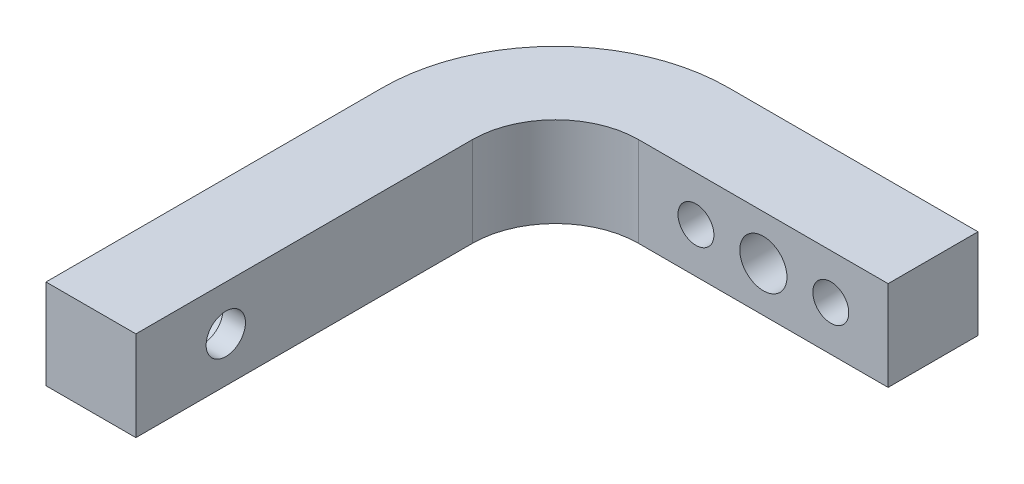
SolidWorks part; units mm, degrees
ref_plane "Front Plane" through (0, 0, 0) normal (0, 0, 1) x (1, 0, 0)
ref_plane "Top Plane" through (0, 0, 0) normal (0, 1, 0) x (1, 0, 0)
ref_plane "Right Plane" through (0, 0, 0) normal (1, 0, 0) x (0, 0, -1)
ref_axis "Z" through (0, 0, -2.892) along (0, 0, 1)
sketch "Sketch1" plane through (0, 0, 0) normal (0, 1, 0) x (1, 0, 0)
  line L0 (-11.1, 0) -> (11.1, 0)
  line L1 (-26.5, -15.4) -> (-26.5, -45.34)
  line L2 (-26.5, -45.34) -> (-18.5, -45.34)
  line L3 (-18.5, -45.34) -> (-18.5, -15.4)
  line L4 (-11.1, -8) -> (11.1, -8)
  line L5 (0, -8) -> (0, 0) construction
  line L6 (18.5, -45.34) -> (18.5, -15.4) construction
  line L7 (26.5, -45.34) -> (18.5, -45.34) construction
  line L8 (26.5, -15.4) -> (26.5, -45.34) construction
  line L9 (11.1, 0) -> (11.1, -8)
  arc A0 (-11.1, 0) -> (-26.5, -15.4) centre (-11.1, -15.4) ccw
  arc A1 (-18.5, -15.4) -> (-11.1, -8) centre (-11.1, -15.4) cw
  arc A2 (18.5, -15.4) -> (11.1, -8) centre (11.1, -15.4) ccw construction
  arc A3 (11.1, 0) -> (26.5, -15.4) centre (11.1, -15.4) cw construction
  dimension "D3" = 7.4
  dimension "D1" = 37
  dimension "D2" = 8
  dimension "D4" = 37.34
extrude "Boss-Extrude1" add sketch "Sketch1" along normal blind 4 and the other way blind 4
sketch "Sketch2" plane through (-18.5, 0, 0) normal (-1, 0, 0) x (0, 0, 1)
  line L1 (31.68, 0) -> (-31.68, 0) construction
  line L2 (0, -4.4) -> (0, 4.4) construction
  circle A0 centre (37.34, 0) radius 1.75
  dimension "D1" = 3.5
  dimension "D2" = 37.34
extrude "Cut-Extrude1" cut sketch "Sketch2" against normal through all both and the other way through all
ref_axis "Axis2" through (-60.1767, 0, 37.34) along (1, 0, 0)
sketch "Sketch3" plane through (0, 0, 0) normal (0, 0, -1) x (-1, 0, 0)
  line L0 (-6, 0) -> (6, 0) construction
  circle A0 centre (0, 0) radius 2.1
  circle A1 centre (-6, 0) radius 1.6
  circle A2 centre (6, 0) radius 1.6
  dimension "D1" = 4.2
  dimension "D3" = 3.2
  dimension "D2" = 12
extrude "Cut-Extrude2" cut sketch "Sketch3" against normal through all
sketch "Sketch4" plane through (-26.5, 0, 0) normal (1, 0, 0) x (0, 0, -1)
  circle A0 centre (-37.34, 0) radius 2.275
  circle A1 centre (-37.34, 0) radius 1.75 construction
  dimension "D1" = 4.55
extrude "Cut-Extrude3" cut sketch "Sketch4" along normal blind 6
sketch "Sketch5" plane through (-26.5, 0, 0) normal (-1, 0, 0) x (0, 0, 1)
  circle A0 centre (37.34, 0) radius 3.825
  dimension "D1" = 7.65
extrude "Cut-Extrude4" cut sketch "Sketch5" against normal blind 0.75
equation "\"width\"= \"EyeDiameter\" + \"EyeClearance\""
equation "\"prongwidth\"= 8"
equation "\"D2@Sketch1\"=\"prongwidth\""
equation "\"D3@Sketch1\"=\"width\"/5"
equation "\"pronglength\"= \"BasePlaneDistance\"'model implicitly adds clearance (of prongwidth) to the hole drilled at the baseplanedistance"
equation "\"D4@Sketch1\"=\"pronglength\""
equation "\"D1@Boss-Extrude1\"=\"prongwidth\"/2"
equation "\"D2@Boss-Extrude1\"=\"prongwidth\"/2"
equation "\"lbracket-plane-to-axis\"= \"BasePlaneDistance\""
equation "\"D2@Sketch2\"=\"lbracket-plane-to-axis\""
equation "\"EyeDiameter\" = 35"
equation "\"BasePlaneDistance\" = \"EyeDiameter\"/2+19.84"
equation "\"EyeClearance\" = 2"
equation "\"D1@Sketch1\"=\"EyeDiameter\"+\"EyeClearance\""
equation "\"BearingDepth\"= 6"
equation "\"BearingHousingID\"=4.5"
equation "\"D1@Sketch4\"=\"BearingHousingID\" + \"PrinterFilamentThickness\" * \"ApplyPrinterOffset\" / 2"
equation "\"D1@Cut-Extrude3\"=\"BearingDepth\""
equation "\"BearingFlangeThickness\"= 0.75"
equation "\"BearingFlangeOD\"=7.5"
equation "\"D1@Sketch5\"=\"BearingFlangeOD\" + \"PrinterFilamentThickness\"*1.5 *\"ApplyPrinterOffset\""
equation "\"D1@Cut-Extrude4\"=\"BearingFlangeThickness\""
equation "\"PrinterFilamentThickness\"= 0.1"
equation "\"ApplyPrinterOffset\"= 1'if 1, adjust hole sizes to try and make pressfits work with the 3d printer"
